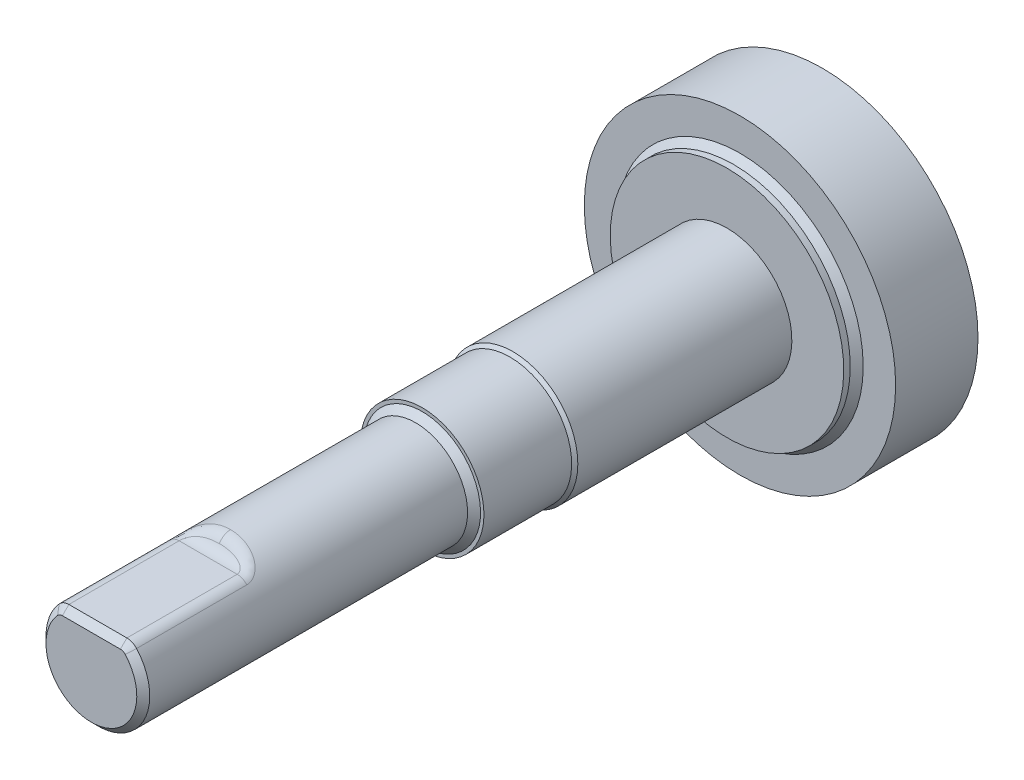
SolidWorks part; units mm, degrees
material "Alloy Steel (SS)"
ref_plane "Front Plane" through (0, 0, 0) normal (0, 0, 1) x (1, 0, 0)
ref_plane "Top Plane" through (0, 0, 0) normal (0, 1, 0) x (1, 0, 0)
ref_plane "Right Plane" through (0, 0, 0) normal (1, 0, 0) x (0, 0, -1)
sketch "Sketch1" plane through (0, 0, 0) normal (1, 0, 0) x (0, 0, -1)
  line L0 (0, 0) -> (-49, 0)
  line L3 (-49, 0) -> (-49, 4)
  line L4 (-17, 5) -> (0, 5)
  line L5 (1, 9) -> (1, 12)
  line L6 (1, 12) -> (7.35, 12)
  line L7 (7.35, 12) -> (7.35, 0)
  line L8 (7.35, 0) -> (0, 0)
  line L9 (1, 9) -> (0, 9)
  line L10 (0, 9) -> (0, 5)
  line L11 (-17, 5) -> (-17, 4.7625)
  line L12 (-17, 4.7625) -> (-23.5, 4.7625)
  line L13 (-23.5, 4.7625) -> (-23.5, 4)
  line L14 (-23.5, 4) -> (-49, 4)
  dimension "D2" = 5
  dimension "D3" = 12
  dimension "D4" = 6.35
  dimension "D5" = 17
  dimension "D6" = 1
  dimension "D7" = 9
  dimension "D9" = 6.5
  dimension "D10" = 4.7625
  dimension "D11" = 32
  dimension "D12" = 4
revolve "Revolve1" add sketch "Sketch1" angle 360 about L8
cosmetic thread "Cosmetic Thread1" parameters "D2"=8.2652
hole_wizard "M2.5 Tapped Hole1" positions "Sketch6" profile "Sketch5" tap size "M2.5" standard "DIN"
sketch "Sketch6" plane through (0, 0, -7.35) normal (0, 0, 1) x (1, 0, 0)
  line L0 (0, 0) -> (1.3892, 7.8785) construction
  line L2 (0, 0) -> (-1.3892, -7.8785) construction
  line L4 (0, 0) -> (0, 9.3499) construction
  point P0 (1.3892, 7.8785)
  point P6 (7.5175, 2.7362)
  point P7 (6.1284, -5.1423)
  point P8 (-1.3892, -7.8785)
  point P9 (-7.5175, -2.7362)
  point P10 (-6.1284, 5.1423)
  dimension "D2" = 8
  dimension "D3" = 8
  dimension "D4" = 10
  dimension "D1" = 6
cosmetic thread "Hole Thread3" parameters "D1"=4, "D2"=2.5
cosmetic thread "Hole Thread4" parameters "D1"=4, "D2"=2.5
cosmetic thread "Hole Thread5" parameters "D1"=4, "D2"=2.5
cosmetic thread "Hole Thread6" parameters "D1"=4, "D2"=2.5
cosmetic thread "Hole Thread7" parameters "D1"=4, "D2"=2.5
cosmetic thread "Hole Thread8" parameters "D1"=4, "D2"=2.5
sketch "Sketch5" plane through (1.3892, 7.8785, -7.35) normal (1, 0, 0) x (0, 1, 0)
  line L0 (0, 0) -> (0, 5.9659)
  line L1 (0, 5.9659) -> (1.025, 5.35)
  line L2 (1.025, 5.35) -> (1.025, 0)
  line L5 (1.025, 0) -> (0, 0)
  line L10 (0, 5.9659) -> (-1.025, 5.35) construction
  line L11 (0, -6.35) -> (0, 107.95) construction
  dimension "Tap Drill Dia." = 2.05
  dimension "Tap Drill Depth" = 5.35
  dimension "Drill Angle" = 118
sketch "Sketch8" plane through (0, 0, 49) normal (0, 0, 1) x (1, 0, 0)
  line L0 (-2.6458, 3) -> (2.6458, 3)
  line L1 (0, 0) -> (0, 3) construction
  circle A0 centre (0, 0) radius 4 construction
  arc A1 (2.6458, 3) -> (-2.6458, 3) centre (0, 0) ccw
  circle A2 centre (0, 0) radius 4 construction
  dimension "D1" = 3
extrude "Cut-Extrude1" cut sketch "Sketch8" against normal blind 10
fillet "Fillet2" radius 1 1 edges at (0, 3, 39)
fillet "Fillet3" radius 1 4 edges at (2.6458, 3, 44.5) (2.2954, 3.2758, 39.3104) (-2.3165, 3.261, 39.3263) (-2.6458, 3, 44.5)
chamfer "Chamfer1" distance 0.5 angle 45 7 edges at (0, -4, 49) (0, 3, 49) (2.6443, 2.9129, 49) (-2.6443, 2.9129, 49) (0, 5, 17) (0, 4, 23.5) (0, 9, -1)
